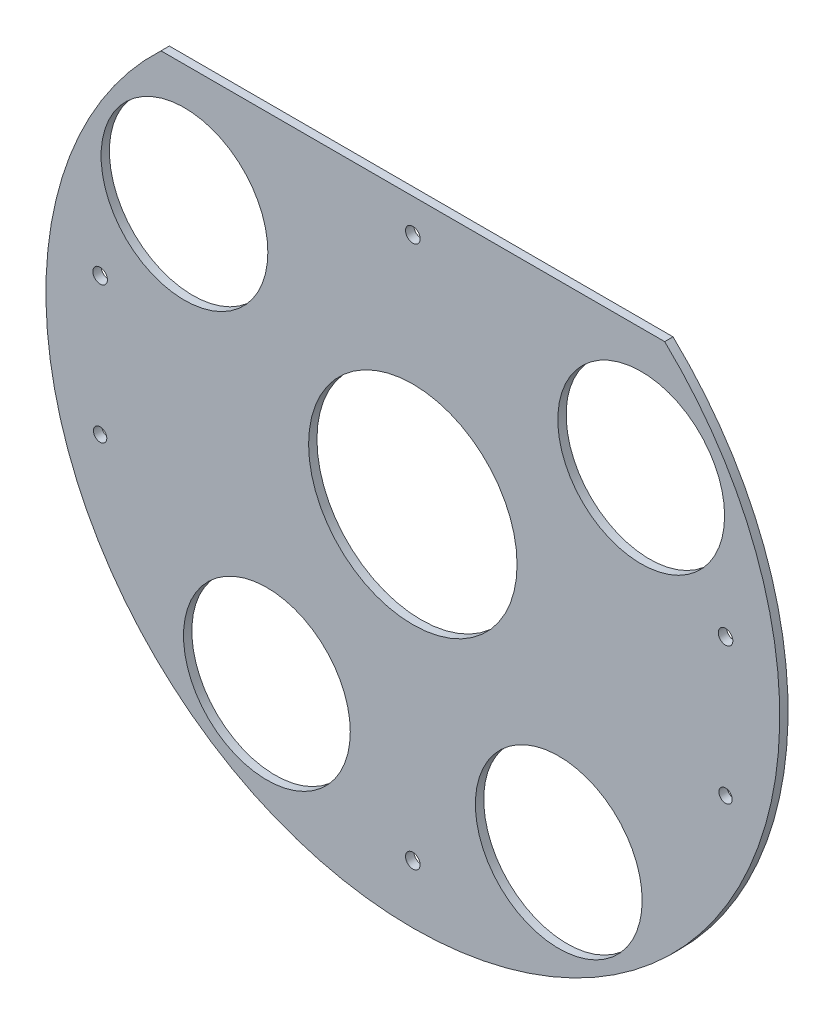
SolidWorks part; units mm, degrees
material "尼龙 101"
ref_plane "前视基准面" through (0, 0, 0) normal (0, 0, 1) x (1, 0, 0)
ref_plane "上视基准面" through (0, 0, 0) normal (0, 1, 0) x (1, 0, 0)
ref_plane "右视基准面" through (0, 0, 0) normal (1, 0, 0) x (0, 0, -1)
sketch "Sketch1" plane through (0, 0, 0) normal (0, 0, 1) x (1, 0, 0)
  line L0 (-60.3987, 64) -> (60.3987, 64)
  arc A0 (-60.3987, 64) -> (60.3987, 64) centre (0, 0) ccw
  circle A1 centre (0, 0) radius 25
  circle A2 centre (-35, -54.7723) radius 20
  circle A3 centre (-54.7723, 35) radius 20
  circle A4 centre (54.7723, 35) radius 20
  circle A5 centre (35, -54.7723) radius 20
  circle A6 centre (0, 0) radius 65 construction
  circle A7 centre (-75, 10) radius 1.75
  circle A8 centre (0, 56) radius 1.75
  circle A9 centre (0, -74) radius 1.75
  circle A10 centre (75, 10) radius 1.75
  circle A11 centre (-75, -23) radius 1.6
  circle A12 centre (75, -23) radius 1.6
  dimension "D1" = 176
  dimension "D3" = 50
  dimension "D4" = 35
  dimension "D5" = 40
  dimension "D6" = 40
  dimension "D7" = 35
  dimension "D11" = 130
  dimension "D8" = 40
  dimension "D9" = 40
  dimension "D10" = 3.5
  dimension "D12" = 3.5
  dimension "D13" = 3.5
  dimension "D18" = 3.5
  dimension "D20" = 3.2
  dimension "D22" = 3.2
  dimension "D2" = 64
  dimension "D14" = 56
  dimension "D15" = 74
  dimension "D16" = 75
  dimension "D17" = 10
  dimension "D19" = 150
  dimension "D21" = 23
  dimension "D23" = 150
extrude "Extrude1" add sketch "Sketch1" along normal blind 0.5
sketch "Sketch2" plane through (0, 0, 0.5) normal (0, 0, 1) x (1, 0, 0)
  line L1 (60.3987, 64) -> (-60.3987, 64)
  line L2 (60.3987, 64) -> (-60.3987, 64)
  circle A1 centre (75, -23) radius 1.6
  circle A2 centre (75, -23) radius 1.6
  circle A3 centre (-75, -23) radius 1.6
  circle A4 centre (-75, -23) radius 1.6
  circle A5 centre (75, 10) radius 1.75
  circle A6 centre (75, 10) radius 1.75
  circle A7 centre (0, -74) radius 1.75
  circle A8 centre (0, -74) radius 1.75
  circle A9 centre (-75, 10) radius 1.75
  circle A10 centre (-75, 10) radius 1.75
  circle A11 centre (54.7723, 35) radius 20
  circle A12 centre (54.7723, 35) radius 20
  circle A13 centre (-35, -54.7723) radius 20
  circle A14 centre (-35, -54.7723) radius 20
  circle A15 centre (0, 0) radius 25
  circle A16 centre (0, 0) radius 25
  circle A17 centre (-54.7723, 35) radius 20
  circle A18 centre (-54.7723, 35) radius 20
  circle A19 centre (35, -54.7723) radius 20
  circle A20 centre (35, -54.7723) radius 20
  circle A21 centre (0, 56) radius 1.75
  circle A22 centre (0, 56) radius 1.75
  arc A23 (-60.3987, 64) -> (60.3987, 64) centre (0, 0) ccw
  arc A24 (-60.3987, 64) -> (60.3987, 64) centre (0, 0) ccw
  dimension "D1" = 0
  dimension "D2" = 0
  dimension "D3" = 0
  dimension "D4" = 0
  dimension "D5" = 0
  dimension "D6" = 0
  dimension "D7" = 0
  dimension "D8" = 0
  dimension "D9" = 0
  dimension "D10" = 0
  dimension "D11" = 0
  dimension "D12" = 0
extrude "Boss-Extrude1" add sketch "Sketch2" along normal blind 1.5
